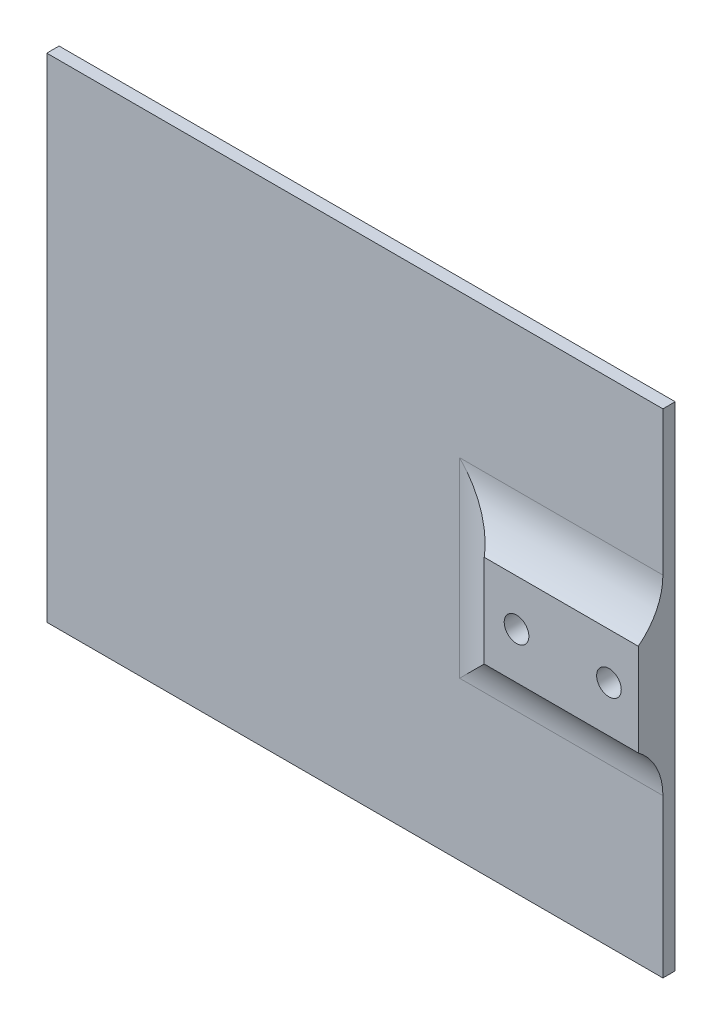
SolidWorks part; units mm, degrees
ref_plane "Front Plane" through (0, 0, 0) normal (0, 0, 1) x (1, 0, 0)
ref_plane "Top Plane" through (0, 0, 0) normal (0, 1, 0) x (1, 0, 0)
ref_plane "Right Plane" through (0, 0, 0) normal (1, 0, 0) x (0, 0, -1)
sketch "Sketch1" plane through (0, 0, 0) normal (0, 0, 1) x (1, 0, 0)
  line L1 (0, 0) -> (100, 0)
  line L2 (0, 0) -> (0, 80)
  line L3 (0, 80) -> (100, 80)
  line L4 (100, 0) -> (100, 80)
  dimension "D1" = 100
  dimension "D2" = 80
extrude "Boss-Extrude1" add sketch "Sketch1" along normal blind 2
sketch "Sketch2" plane through (0, 0, 2) normal (0, 0, 1) x (1, 0, 0)
  line L0 (100, 0) -> (100, 80) construction
  line L1 (100, 33.637) -> (75, 33.637)
  line L2 (100, 33.637) -> (100, 48.637)
  line L3 (100, 48.637) -> (75, 48.637)
  line L4 (75, 33.637) -> (75, 48.637)
  dimension "D1" = 25
  dimension "D2" = 15
extrude "Boss-Extrude2" add sketch "Sketch2" along normal blind 4
sketch "Sketch3" plane through (0, 0, 6) normal (0, 0, 1) x (1, 0, 0)
  line L0 (100, 33.637) -> (100, 48.637) construction
  line L5 (75, 41.137) -> (100, 41.137) construction
  line L6 (75, 48.637) -> (75, 33.637) construction
  circle A0 centre (80.2429, 41.137) radius 2
  circle A1 centre (95.2429, 41.137) radius 2
  point P11 (82.4759, 41.137)
  point P12 (80.2429, 41.137)
  dimension "D2" = 4
  dimension "D1" = 15
extrude "Cut-Extrude1" cut sketch "Sketch3" against normal through all
fillet "Fillet1" radius 10 3 edges at (87.5, 48.637, 2) (75, 41.137, 2) (87.5, 33.637, 2)
